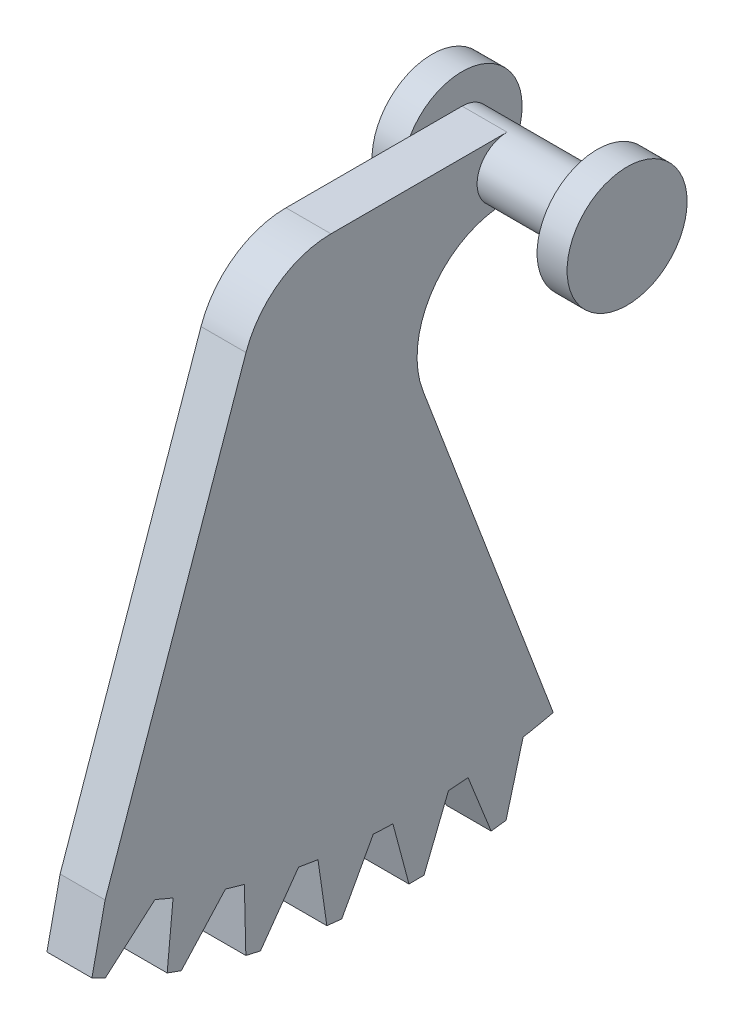
SolidWorks part; units mm, degrees
material "AISI 1045 Steel, cold drawn"
ref_plane "Front Plane" through (0, 0, 0) normal (1, 0, 0) x (0, 1, 0)
ref_plane "Top Plane" through (0, 0, 0) normal (0, 0, 1) x (0, 1, 0)
ref_plane "Right Plane" through (0, 0, 0) normal (0, 1, 0) x (-1, 0, 0)
sketch "Sketch1" plane through (0, 0, 0) normal (1, 0, 0) x (0, 1, 0)
  circle A0 centre (0, 0) radius 4
  circle A1 centre (0, 0) radius 2
  dimension "D1" = 8
  dimension "D2" = 4
extrude "Boss-Extrude1" add sketch "Sketch1" against normal blind 2 contours A0
extrude "Boss-Extrude2" add sketch "Sketch1<3>" against normal blind 9 from surface contours A1 starting at face at (-2, 0, -4)
sketch "Sketch1<3>" plane through (0, 0, 0) normal (1, 0, 0) x (0, 1, 0) same geometry as "Sketch1"
extrude "Boss-Extrude3" add sketch "Sketch1<4>" against normal blind 2 from surface contours A0 starting at face at (-11, 0, -2)
sketch "Sketch1<4>" plane through (0, 0, 0) normal (1, 0, 0) x (0, 1, 0) same geometry as "Sketch1"
sketch "Sketch2" plane through (-11, 0, 0) normal (1, 0, 0) x (0, 1, 0)
  line L0 (-32.7556, 28.1304) -> (-34.4432, 28.7194)
  line L1 (-7.0697, 0) -> (10.7075, 0) construction
  line L2 (0, 6.8393) -> (0, -8.3542) construction
  line L3 (2, 16) -> (2, 0)
  line L4 (-33.0473, -3.078) -> (-10.1267, 5.6104)
  line L5 (-28.931, 26.7955) -> (2, 16)
  line L6 (-33.0473, -3.078) -> (-36.8186, -4.5075)
  line L7 (8.12, 6.47) -> (-33.6692, 26.3298) construction
  line L8 (8.12, 6.47) -> (-43.8505, 33.9756) construction
  line L9 (4.5625, 16) -> (-39.632, 16) construction
  line L11 (-30.5685, 23.4732) -> (-33.4416, 26.7831)
  line L12 (-33.4416, 26.7831) -> (-32.9928, 27.6767)
  line L13 (-32.9928, 27.6767) -> (-28.1414, 26.6242)
  arc A0 (-2, 0) -> (-10.1267, 5.6104) centre (-8, 0) ccw
  arc A1 (-28.931, 26.7955) -> (-33.0473, -3.078) centre (8.12, 6.47) ccw
  arc A2 (-32.438, 28.7194) -> (-36.8186, -4.5075) centre (8.12, 6.47) ccw
  arc A3 (-32.438, 28.7194) -> (-36.9438, -3.9817) centre (8.12, 6.47) ccw construction
  circle A6 centre (0, 0) radius 2 construction
  circle A7 centre (0, 0) radius 2
  dimension "D5" = 12
  dimension "D8" = 84.52
  dimension "D1" = 109.24
  dimension "D2" = 6.47
  dimension "D3" = 8.12
  dimension "D4" = 2
  dimension "D6" = 8
  dimension "D7" = 40
  dimension "D9" = 16
  dimension "D10" = 4
  dimension "D11" = 1.5072
  dimension "D12" = 7
  dimension "D13" = 323.2
  dimension "D14" = 1
extrude "Boss-Extrude4" add sketch "Sketch2" along normal blind 3
fillet "Fillet1" radius 6 1 edges at (-9.5, 2, 16)
extrude "Boss-Extrude5" add sketch "Sketch2<3>" along normal blind 3 contours A1 L13 L12 L11 region at (-11, -31.1665, 25.9899)
sketch "Sketch2<3>" plane through (-11, 0, 0) normal (1, 0, 0) x (0, 1, 0) same geometry as "Sketch2"
pattern_circular "CirPattern1" count 6 over 34 about axis through (-8, 8.12, 6.47) along (1, 0, 0) of "Boss-Extrude5"
ref_plane "Plane1" through (0, 0, 16) normal (0, 0, 1) x (0, -1, 0)
